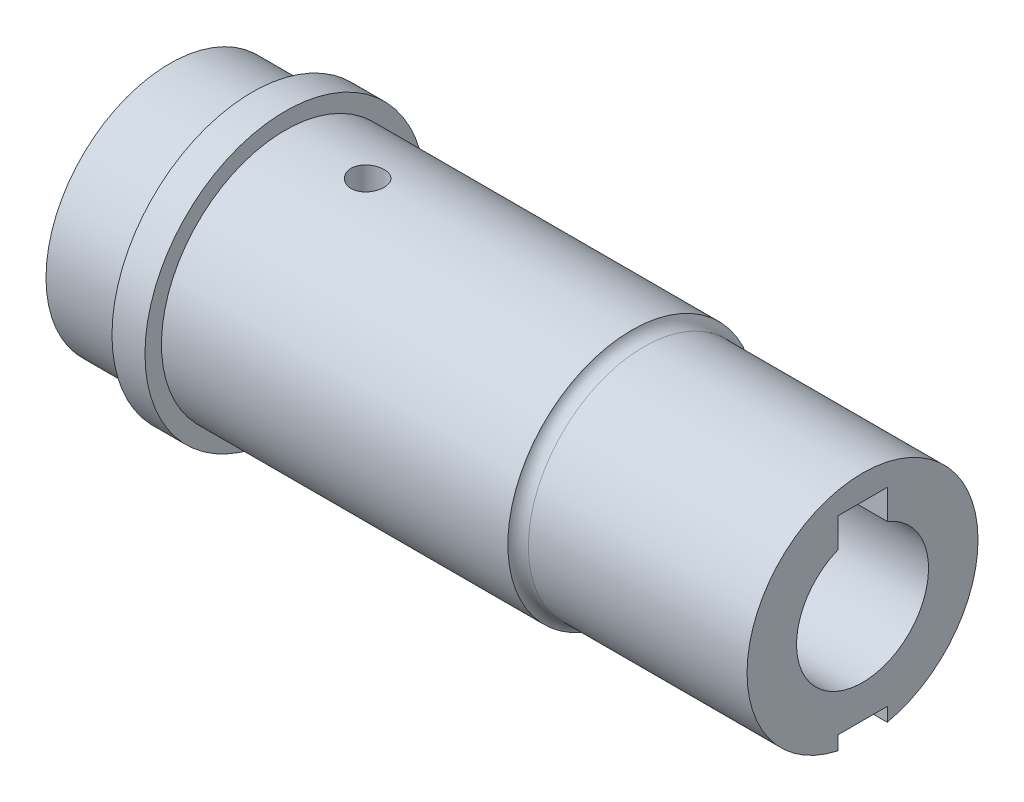
SolidWorks part; units mm, degrees
material "Plain Carbon Steel"
ref_plane "Front Plane" through (0, 0, 0) normal (0, 0, 1) x (1, 0, 0)
ref_plane "Top Plane" through (0, 0, 0) normal (0, 1, 0) x (1, 0, 0)
ref_plane "Right Plane" through (0, 0, 0) normal (1, 0, 0) x (0, 0, -1)
sketch "Sketch1" plane through (0, 0, 0) normal (1, 0, 0) x (0, 0, -1)
  circle A0 centre (0, 0) radius 7.5
  dimension "D1" = 15
extrude "Boss-Extrude1" add sketch "Sketch1" along normal blind 5
sketch "Sketch2" plane through (5, 0, 0) normal (1, 0, 0) x (0, 0, -1)
  circle A0 centre (0, 0) radius 8.5
  dimension "D1" = 17
extrude "Boss-Extrude2" add sketch "Sketch2" along normal blind 2
sketch "Sketch3" plane through (7, 0, 0) normal (1, 0, 0) x (0, 0, -1)
  circle A0 centre (0, 0) radius 7.5
  dimension "D1" = 15
extrude "Boss-Extrude3" add sketch "Sketch3" along normal blind 35
sketch "Sketch4" plane through (0, 0, 0) normal (-1, 0, 0) x (0, 0, 1)
  circle A0 centre (0, 0) radius 4
  dimension "D1" = 8
extrude "Cut-Extrude1" cut sketch "Sketch4" against normal through all
ref_plane "Plane1" through (0, 7.5, 0) normal (0, 1, 0) x (1, 0, 0)
sketch "Sketch7" plane through (0, 7.5, 0) normal (0, 1, 0) x (1, 0, 0)
  line L0 (-2.75, 0) -> (2.75, 0) construction
  line L1 (0, -8.25) -> (0, 8.25) construction
  circle A0 centre (12, 0) radius 1
  dimension "D1" = 2
  dimension "D2" = 12
extrude "Cut-Extrude3" cut sketch "Sketch7" against normal up to next
sketch "Sketch8" plane through (42, 0, 0) normal (1, 0, 0) x (0, 0, -1)
  line L0 (0, 2.75) -> (0, -2.75) construction
  line L1 (-1.5, -9) -> (1.5, -9)
  line L2 (-1.5, -9) -> (-1.5, -6)
  line L3 (-1.5, -6) -> (1.5, -6)
  line L4 (1.5, -9) -> (1.5, -6)
  line L5 (-1.5, -9) -> (1.5, -6) construction
  line L6 (-1.5, -6) -> (1.5, -9) construction
  circle A0 centre (0, 0) radius 7.5 construction
  point P0 (0, -7.5)
  dimension "D1" = 3
  dimension "D2" = 1.5
extrude "Cut-Extrude5" cut sketch "Sketch8" against normal blind 33
sketch "Sketch9" plane through (42, 0, 0) normal (1, 0, 0) x (0, 0, -1)
  circle A0 centre (0, 0) radius 7.5
  circle A1 centre (0, 0) radius 7
  dimension "D1" = 15
  dimension "D2" = 14
extrude "Cut-Extrude6" cut sketch "Sketch9" against normal blind 14
fillet "Fillet1" radius 0.8 1 edges at (28, 7, 0)
sketch "Sketch10" plane through (0, 0, 0) normal (-1, 0, 0) x (0, 0, 1)
  line L1 (-1.5, 2.5) -> (1.5, 2.5)
  line L2 (-1.5, 2.5) -> (-1.5, 5.5)
  line L3 (-1.5, 5.5) -> (1.5, 5.5)
  line L4 (1.5, 2.5) -> (1.5, 5.5)
  line L5 (-1.5, 2.5) -> (1.5, 5.5) construction
  line L6 (-1.5, 5.5) -> (1.5, 2.5) construction
  circle A0 centre (0, 0) radius 4 construction
  point P0 (0, 4)
  point P7 (0, 0)
  dimension "D1" = 3
  dimension "D2" = 3
extrude "Cut-Extrude7" cut sketch "Sketch10" against normal through all
